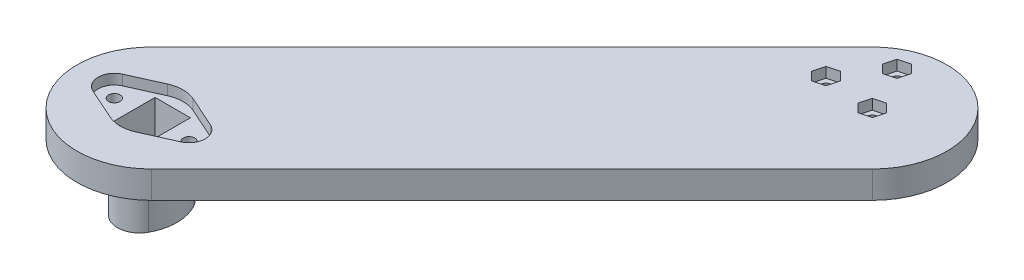
SolidWorks part; units mm, degrees
ref_plane "Front Plane" through (0, 0, 0) normal (0, 0, 1) x (1, 0, 0)
ref_plane "Top Plane" through (0, 0, 0) normal (0, 1, 0) x (1, 0, 0)
ref_plane "Right Plane" through (0, 0, 0) normal (1, 0, 0) x (0, 0, -1)
sketch "Sketch1" plane through (0, 0, 0) normal (0, 1, 0) x (1, 0, 0)
  line L0 (0, 0) -> (106.066, 106.066) construction
  line L25 (-15.5563, 15.5563) -> (90.5097, 121.6224)
  line L26 (15.5563, -15.5563) -> (121.6224, 90.5097)
  line L27 (106.066, 106.066) -> (-1.0853, 181.0942) construction
  line L28 (97.4624, 93.7787) -> (-9.689, 168.8069)
  line L29 (114.6697, 118.3533) -> (7.5183, 193.3815)
  line L30 (99.7189, 119.6662) -> (91.1152, 107.3789) construction
  line L31 (106.9626, 109.4121) -> (103.6165, 108.5155)
  line L32 (103.6165, 108.5155) -> (102.72, 105.1694)
  line L33 (102.72, 105.1694) -> (105.1694, 102.72)
  line L34 (105.1694, 102.72) -> (108.5155, 103.6165)
  line L35 (108.5155, 103.6165) -> (109.4121, 106.9626)
  line L36 (109.4121, 106.9626) -> (106.9626, 109.4121)
  line L37 (97.2329, 93.4511) -> (-9.9184, 168.4793)
  line L38 (90.2186, 104.0328) -> (93.5647, 104.9294)
  line L39 (93.5647, 104.9294) -> (94.4613, 108.2754)
  line L40 (94.4613, 108.2754) -> (92.0118, 110.7249)
  line L41 (92.0118, 110.7249) -> (88.6657, 109.8284)
  line L42 (88.6657, 109.8284) -> (87.7692, 106.4823)
  line L43 (87.7692, 106.4823) -> (90.2186, 104.0328)
  line L44 (100.6154, 123.0122) -> (97.2694, 122.1156)
  line L45 (97.2694, 122.1156) -> (96.3728, 118.7696)
  line L46 (96.3728, 118.7696) -> (98.8223, 116.3201)
  line L47 (98.8223, 116.3201) -> (102.1684, 117.2167)
  line L48 (102.1684, 117.2167) -> (103.0649, 120.5627)
  line L49 (103.0649, 120.5627) -> (100.6154, 123.0122)
  line L66 (114.8991, 118.681) -> (7.7477, 193.7091)
  line L67 (-5.7, 6.7) -> (-5.7, -6.7)
  line L68 (-5.2, 6.2) -> (5.2, 6.2)
  line L69 (-5.2, 6.2) -> (-5.2, -6.2)
  line L70 (-5.2, -6.2) -> (5.2, -6.2)
  line L71 (5.2, 6.2) -> (5.2, -6.2)
  line L72 (-5.7, -6.7) -> (5.7, -6.7)
  line L73 (5.7, 6.7) -> (5.7, -6.7)
  line L74 (-5.7, 6.7) -> (5.7, 6.7)
  line L75 (-11, 0) -> (11, 0) construction
  circle A7 centre (0, 0) radius 2.5 construction
  circle A8 centre (0, 0) radius 4.5
  arc A9 (-5.7, 6.7) -> (5.7, 6.7) centre (0, 3.5564) cw
  arc A10 (-5.7, 6.7) -> (-5.7, -6.7) centre (6.4485, 0) ccw
  arc A12 (-15.5563, 15.5563) -> (15.5563, -15.5563) centre (0, 0) ccw
  arc A13 (121.6224, 90.5097) -> (90.5097, 121.6224) centre (106.066, 106.066) ccw
  arc A14 (97.4624, 93.7787) -> (114.6697, 118.3533) centre (106.066, 106.066) ccw
  arc A15 (7.5183, 193.3815) -> (-9.689, 168.8069) centre (-1.0853, 181.0942) ccw
  circle A16 centre (106.066, 106.066) radius 1.7
  circle A17 centre (106.066, 106.066) radius 3 construction
  circle A18 centre (99.7189, 119.6662) radius 1.7
  circle A19 centre (91.1152, 107.3789) radius 1.7
  circle A20 centre (91.1152, 107.3789) radius 3 construction
  circle A21 centre (99.7189, 119.6662) radius 3 construction
  arc A22 (7.7477, 193.7091) -> (-9.9184, 168.4793) centre (-1.0853, 181.0942) ccw
  arc A23 (97.2329, 93.4511) -> (114.8991, 118.681) centre (106.066, 106.066) ccw
  arc A24 (-5.7, -6.7) -> (5.7, -6.7) centre (0, -3.5564) ccw
  arc A25 (5.7, -6.7) -> (5.7, 6.7) centre (-6.4485, 0) ccw
  circle A26 centre (11, 0) radius 1.7
  circle A27 centre (-11, 0) radius 1.7
  point P6 (5.2, 0)
  point P10 (0, 6.2)
  point P14 (53.033, 53.033)
  point P50 (52.4903, 143.5801)
  point P66 (95.417, 113.5225)
  dimension "D4" = 10.4
  dimension "D5" = 5
  dimension "D6" = 9
  dimension "D7" = 0.5
  dimension "D8" = 3.4
  dimension "D3" = 12.4
  dimension "D9" = 3.4
  dimension "D10" = 22
  dimension "D13" = 22
  dimension "D17" = 15
  dimension "D18" = 3.4
  dimension "D19" = 6
  dimension "D20" = 3.4
  dimension "D22" = 3.4
  dimension "D23" = 6
  dimension "D24" = 6
  dimension "D14" = 45
  dimension "D15" = 150
  dimension "D16" = 80
  dimension "D21" = 15
  dimension "D25" = 13
  dimension "D26" = 0.4
extrude "Boss-Extrude1" add sketch "Sketch1" along normal blind 8 contours L26 A13 L25 A12
extrude "Boss-Extrude2" add sketch "Sketch1<4>" against normal blind 24.8 from surface contours L74 L67 L72 L73 L68 L71 L70 L69 | A9 L74 | L73 A25 | L72 A24 | L67 A10 starting at face at (53.033, 8, -53.033)
sketch "Sketch1<4>" plane through (0, 0, 0) normal (0, 1, 0) x (1, 0, 0) same geometry as "Sketch1"
extrude "Cut-Extrude3" cut sketch "Sketch1<6>" along normal through all both and the other way through all from offset 5 contours A12 | A12 | L71 L68 L69 L70 A8 | A8 | A27 | A26 | A18 | A19 | A16 region at (0, 0, -6.0382) region at (0, 0, 0) region at (106.066, 0, -106.066) region at (99.7189, 0, -119.6662) region at (91.1152, 0, -107.3789) region at (11, 0, 0) region at (-11, 0, 0) offset against normal yes
sketch "Sketch1<6>" plane through (0, 0, 0) normal (0, 1, 0) x (1, 0, 0) same geometry as "Sketch1"
extrude "Boss-Extrude3" add sketch "Sketch1<10>" against normal blind 0.7 from surface contours L74 L67 L72 L73 L68 L71 L70 L69 | L71 L68 L69 L70 A8 | A9 L74 | L73 A25 | L72 A24 | L67 A10 region at (0, 0, -6.5241) region at (0, 0, -8.0815) region at (-6.3938, 0, 0) region at (0, 0, 8.0815) region at (6.3938, 0, 0) region at (0, 0, -6.0382) starting at face at (0, -16.8, 0)
sketch "Sketch1<10>" plane through (0, 0, 0) normal (0, 1, 0) x (1, 0, 0) same geometry as "Sketch1"
sketch "Sketch2" plane through (0, 8, 0) normal (0, 1, 0) x (1, 0, 0)
  line L0 (-3.7841, 8.4406) -> (-12.9432, 4.3343)
  line L1 (-12.9432, -4.3343) -> (-3.7841, -8.4406)
  line L2 (12.9432, -4.3343) -> (3.7841, -8.4406)
  line L3 (12.9432, 4.3343) -> (3.7841, 8.4406)
  line L4 (-11, 0) -> (11, 0) construction
  circle A0 centre (0, 0) radius 9.25
  circle A1 centre (11, 0) radius 4.75
  circle A2 centre (-11, 0) radius 4.75
  dimension "D1" = 9.5
  dimension "D2" = 9.5
  dimension "D3" = 18.5
  dimension "D4" = 22
extrude "Cut-Extrude7" cut sketch "Sketch2" against normal blind 3 contours A2 A0 L0 | A2 L1 A0 | A1 A0 L2 | A1 L3 A0 | A2 | A0 | A1 region at (-8.5208, 8, -5.6136) region at (8.5208, 8, -5.6136) region at (-8.5208, 8, 5.6136) region at (8.5208, 8, 5.6136)
extrude "Cut-Extrude5" cut sketch "Sketch1<8>" against normal blind 3 from surface contours L48 L49 L44 L45 L46 L47 A18 | L42 L43 L38 L39 L40 L41 A19 | L35 L36 L31 L32 L33 L34 A16 region at (108.1204, 0, -108.1204) region at (89.0608, 0, -105.3245) region at (101.7733, 0, -121.7206) starting at face at (0, 8, 0)
sketch "Sketch1<8>" plane through (0, 0, 0) normal (0, 1, 0) x (1, 0, 0) same geometry as "Sketch1"
extrude "Cut-Extrude6" cut sketch "Sketch1<9>" along normal blind 3 from surface contours L66 A22 L37 A23 starting at face at (106.066, 0, -104.366)
sketch "Sketch1<9>" plane through (0, 0, 0) normal (0, 1, 0) x (1, 0, 0) same geometry as "Sketch1"
